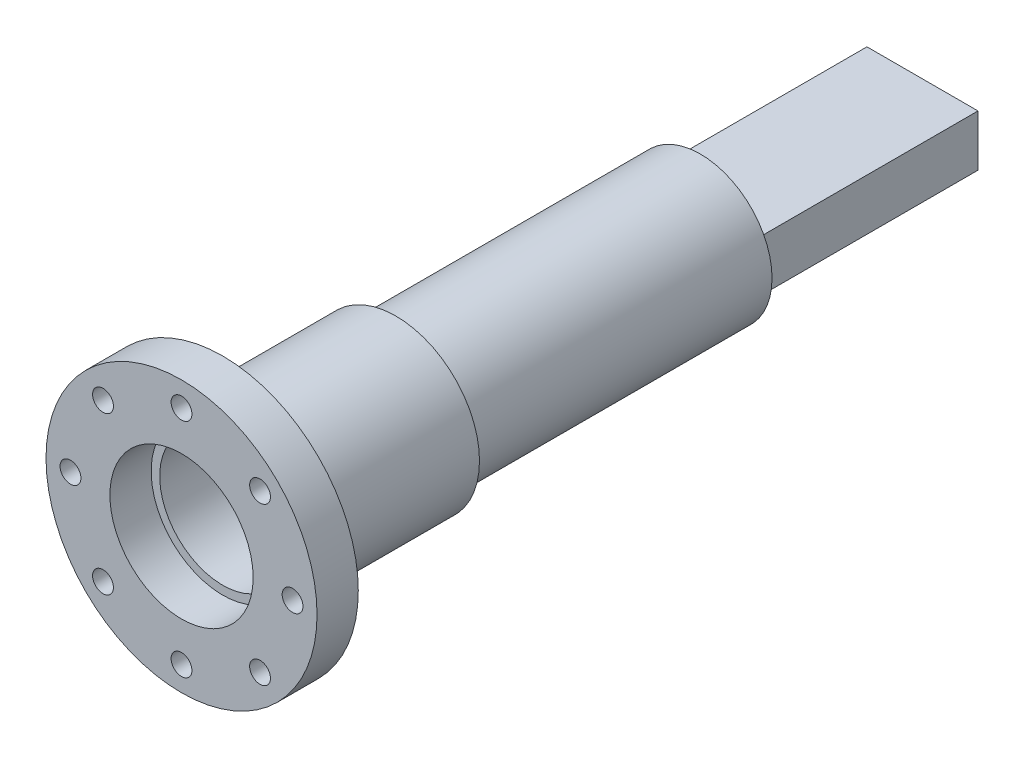
SolidWorks part; units mm, degrees
ref_plane "Front Plane" through (0, 0, 0) normal (0, 0, 1) x (1, 0, 0)
ref_plane "Top Plane" through (0, 0, 0) normal (0, 1, 0) x (1, 0, 0)
ref_plane "Right Plane" through (0, 0, 0) normal (1, 0, 0) x (0, 0, -1)
sketch "Sketch1" plane through (0, 0, 0) normal (0, 0, 1) x (1, 0, 0)
  line L5 (-21.5, -9) -> (21.5, -9)
  line L6 (-21.5, -9) -> (-21.5, 9)
  line L7 (-21.5, 9) -> (21.5, 9)
  line L8 (21.5, -9) -> (21.5, 9)
  line L9 (-21.5, -9) -> (21.5, 9) construction
  line L10 (-21.5, 9) -> (21.5, -9) construction
  line L11 (-23.25, -10.75) -> (23.25, -10.75)
  line L12 (-23.25, -10.75) -> (-23.25, 10.75)
  line L13 (-23.25, 10.75) -> (23.25, 10.75)
  line L14 (23.25, -10.75) -> (23.25, 10.75)
  line L15 (-23.25, -10.75) -> (23.25, 10.75) construction
  line L16 (-23.25, 10.75) -> (23.25, -10.75) construction
  point P0 (0, 0)
  point P6 (0, 0)
  dimension "D1" = 18
  dimension "D2" = 42.9999
  dimension "D3" = 21.5
  dimension "D4" = 46.5
extrude "Boss-Extrude1" add sketch "Sketch1" against normal blind 93.0001 contours L13 L14 L11 L12
shell "Shell1" thickness 3.5
sketch "Sketch2" plane through (0, 0, 0) normal (0, 0, 1) x (1, 0, 0)
  circle A0 centre (0, 0) radius 29.9999
  circle A1 centre (0, 0) radius 26.416
  dimension "D1" = 59.9999
ref_plane "Plane1" through (0, 0, 29.9999) normal (0, 0, 1) x (1, 0, 0)
ref_plane "Plane2" through (0, 0, 59.9999) normal (0, 0, 1) x (1, 0, 0)
ref_plane "Plane3" through (0, 0, 89.9998) normal (0, 0, 1) x (1, 0, 0)
ref_plane "Plane4" through (0, 0, 127.4998) normal (0, 0, 1) x (1, 0, 0)
ref_plane "Plane5" through (0, 0, 149.9998) normal (0, 0, 1) x (1, 0, 0)
ref_plane "Plane6" through (0, 0, 179.9998) normal (0, 0, 1) x (1, 0, 0)
ref_plane "Plane7" through (0, 0, 199.9998) normal (0, 0, 1) x (1, 0, 0)
sketch "Sketch3" plane through (0, 0, 29.9999) normal (0, 0, 1) x (1, 0, 0)
  circle A0 centre (0, 0) radius 29.9999
  circle A1 centre (0, 0) radius 26.416
extrude "Boss-Extrude2" add sketch "Sketch2" along normal up to surface (127.4998 mm away) contours A0 | A1 up to plane "Plane4"
sketch "Sketch13" plane through (0, 0, 89.9998) normal (0, 0, 1) x (1, 0, 0)
  circle A0 centre (0, 0) radius 27.4999
sketch "Sketch14" plane through (0, 0, 149.9998) normal (0, 0, 1) x (1, 0, 0)
  circle A0 centre (0, 0) radius 35.0001
  circle A1 centre (0, 0) radius 26.416
  dimension "D1" = 52.832
sketch "Sketch17" plane through (0, 0, 199.9998) normal (0, 0, 1) x (1, 0, 0)
  circle A0 centre (0, 0) radius 56.75
sketch "Sketch18" plane through (0, 0, 199.9998) normal (0, 0, 1) x (1, 0, 0)
  line L0 (0, 56.75) -> (0, 0) construction
  circle A0 centre (0, 0) radius 56.75 construction
  circle A1 centre (0, 46.5) radius 4.3625
  circle A2 centre (32.8805, 32.8805) radius 4.3625
  circle A3 centre (46.5, 0) radius 4.3625
  circle A4 centre (32.8805, -32.8805) radius 4.3625
  circle A5 centre (0, -46.5) radius 4.3625
  circle A6 centre (-32.8805, -32.8805) radius 4.3625
  circle A7 centre (-46.5, 0) radius 4.3625
  circle A8 centre (-32.8805, 32.8805) radius 4.3625
  circle A9 centre (0, 0) radius 56.75
  circle A10 centre (0, 0) radius 29.9999
  point P23 (0, 0)
  dimension "D3" = 46.5
  dimension "D2" = 93.0001
  dimension "D1" = 8
extrude "Boss-Extrude6" add sketch "Sketch18" along normal blind 17.272
extrude "Boss-Extrude7" add sketch "Sketch14" along normal up to surface (50 mm away) up to plane "Plane7"
extrude "Boss-Extrude8" add sketch "Sketch14<6>" against normal up to surface (22.5 mm away) up to plane "Plane4"
sketch "Sketch14<6>" plane through (0, 0, 149.9998) normal (0, 0, 1) x (1, 0, 0) same geometry as "Sketch14"
sketch "Sketch19" plane through (0, 0, 0) normal (0, 0, 1) x (1, 0, 0)
  line L0 (-19.75, 7.25) -> (19.75, 7.25) construction
  line L5 (-19.75, -7.25) -> (19.75, -7.25)
  line L6 (-19.75, -7.25) -> (-19.75, 7.25)
  line L7 (-19.75, 7.25) -> (19.75, 7.25)
  line L8 (19.75, -7.25) -> (19.75, 7.25)
  line L9 (-19.75, -7.25) -> (19.75, 7.25) construction
  line L10 (-19.75, 7.25) -> (19.75, -7.25) construction
  line L11 (19.75, -7.25) -> (19.75, 7.25) construction
  circle A0 centre (0, 0) radius 27.4999
extrude "Boss-Extrude9" add sketch "Sketch19" along normal blind 0.762
